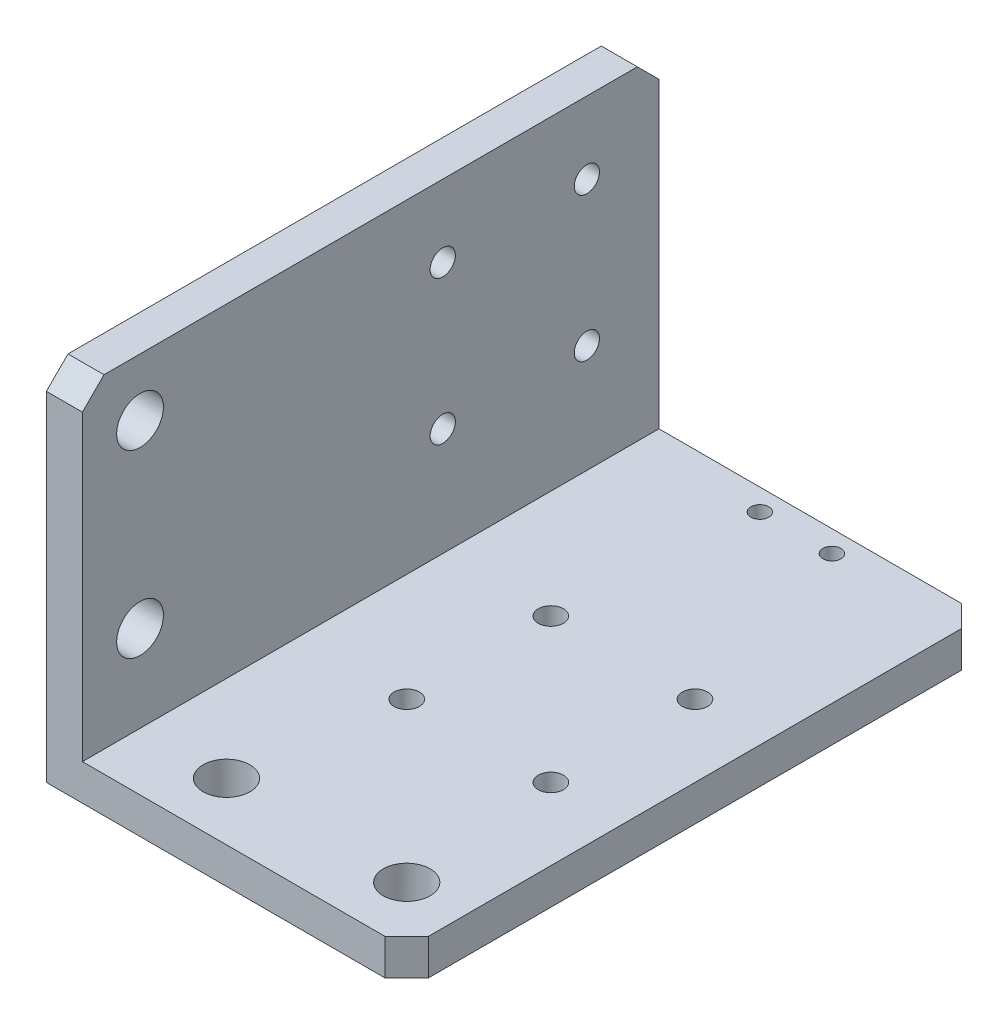
SolidWorks part; units mm, degrees
material "Lega 1060"
ref_plane "Piano frontale" through (0, 0, 0) normal (0, 0, 1) x (1, 0, 0)
ref_plane "Piano superiore" through (0, 0, 0) normal (0, 1, 0) x (1, 0, 0)
ref_plane "Piano destro" through (0, 0, 0) normal (1, 0, 0) x (0, 0, -1)
sketch "Schizzo1" plane through (0, 0, 0) normal (0, 0, 1) x (1, 0, 0)
  line L0 (0, 0) -> (0, 50)
  line L1 (0, 50) -> (5, 50)
  line L2 (5, 50) -> (5, 5)
  line L3 (5, 5) -> (50, 5)
  line L4 (50, 5) -> (50, 0)
  line L5 (50, 0) -> (0, 0)
  dimension "D1" = 5
  dimension "D2" = 5
  dimension "D3" = 50
  dimension "D4" = 50
extrude "Estrusione-Estrusione1" add sketch "Schizzo1" along normal blind 80
sketch "Schizzo2" plane through (0, 0, 0) normal (0, -1, 0) x (1, 0, 0)
  line L0 (5.4524, 72) -> (42.7933, 72) construction
  line L1 (0, 80) -> (50, 80) construction
  line L5 (50, 80) -> (50, 0) construction
  point P4 (17, 72)
  point P5 (42, 72)
  dimension "D1" = 8
  dimension "D2" = 25
  dimension "D3" = 8
sketch "Schizzo3" plane through (0, 0, 0) normal (-1, 0, 0) x (0, 0, 1)
  line L0 (72, 44.621) -> (72, 5.772) construction
  line L1 (80, 50) -> (80, 0) construction
  line L2 (80, 50) -> (0, 50) construction
  point P4 (72, 42)
  point P5 (72, 17)
  dimension "D1" = 8
  dimension "D2" = 8
  dimension "D3" = 25
hole_wizard "Foro Ø6.5 (6.5)-1" positions "Schizzo5" profile "Schizzo4" hole size "Ø6.5" standard "ISO" end condition through all
sketch "Schizzo5" plane through (0, 0, 0) normal (0, -1, 0) x (-1, 0, 0)
  point P0 (-17, -72)
  point P3 (-42, -72)
sketch "Schizzo4" plane through (17, 0, 72) normal (1, 0, 0) x (0, 0, -1)
  line L0 (0, 0) -> (0, 50)
  line L1 (0, 50) -> (3.25, 50)
  line L2 (3.25, 50) -> (3.25, 0)
  line L5 (3.25, 0) -> (0, 0)
  line L11 (0, -6.35) -> (0, 107.95) construction
  dimension "Thru Hole Dia." = 6.5
  dimension "Thru Hole Depth" = 50
hole_wizard "Foro Ø6.5 (6.5)-2" positions "Schizzo7" profile "Schizzo6" hole size "Ø6.5" standard "ISO"
sketch "Schizzo7" plane through (0, 0, 0) normal (-1, 0, 0) x (0, 0, 1)
  point P1 (72, 42)
  point P4 (72, 17)
sketch "Schizzo6" plane through (0, 42, 72) normal (0, 1, 0) x (0, 0, 1)
  line L0 (0, 0) -> (0, 6.9528)
  line L1 (0, 6.9528) -> (3.25, 5)
  line L2 (3.25, 5) -> (3.25, 0)
  line L5 (3.25, 0) -> (0, 0)
  line L10 (0, 6.9528) -> (-3.25, 5) construction
  line L11 (0, -6.35) -> (0, 107.95) construction
  dimension "Hole Dia." = 6.5
  dimension "Hole Depth" = 5
  dimension "Drill Angle" = 118
ref_plane "Piano1" through (0, 0, 40) normal (0, 0, 1) x (1, 0, 0)
sketch "Schizzo8" plane through (0, 0, 0) normal (-1, 0, 0) x (0, 0, 1)
  line L2 (80, 50) -> (80, 0) construction
  line L3 (80, 50) -> (0, 50) construction
  circle A0 centre (20, 30) radius 7
  dimension "D3" = 14
  dimension "D1" = 60
  dimension "D2" = 20
sketch "Schizzo9" plane through (0, 0, 0) normal (0, -1, 0) x (1, 0, 0)
  line L0 (50, 80) -> (50, 0) construction
  line L1 (0, 80) -> (50, 80) construction
  circle A0 centre (30, 40) radius 7
  dimension "D1" = 14
  dimension "D2" = 20
  dimension "D3" = 40
sketch "Schizzo10" plane through (0, 0, 0) normal (-1, 0, 0) x (0, 0, 1)
  line L1 (20, 42.2663) -> (20, 14.8621) construction
  line L2 (19.1906, 30.8094) -> (20, 30) construction
  circle A0 centre (10, 40) radius 1.75
  circle A1 centre (30, 40) radius 1.75
  circle A3 centre (30, 20) radius 1.75
  circle A4 centre (10, 20) radius 1.75
  circle A5 centre (20, 30) radius 7 construction
  point P20 (20, 30)
  dimension "D1" = 3.5
  dimension "D2" = 20
  dimension "D3" = 45
  dimension "D4" = 4
extrude "Taglio-Estrusione3" cut sketch "Schizzo10" against normal up to next
sketch "Schizzo11" plane through (0, 0, 0) normal (0, -1, 0) x (1, 0, 0)
  line L0 (30, 40) -> (14.4837, 40) construction
  line L1 (30, 40) -> (34.5929, 44.5929) construction
  circle A0 centre (20, 30) radius 1.75
  circle A3 centre (20, 50) radius 1.75
  circle A4 centre (40, 50) radius 1.75
  circle A5 centre (40, 30) radius 1.75
  circle A6 centre (30, 40) radius 7 construction
  point P2 (30, 40)
  point P17 (30, 40)
  dimension "D2" = 3.5
  dimension "D1" = 20
  dimension "D3" = 45
  dimension "D4" = 4
extrude "Taglio-Estrusione4" cut sketch "Schizzo11" against normal up to next
chamfer "Smusso1" distance 3 angle 45 4 edges at (2.5, 50, 0) (50, 2.5, 0) (2.5, 50, 80) (50, 2.5, 80)
sketch "Schizzo12" plane through (0, 5, 0) normal (0, 1, 0) x (1, 0, 0)
  line L0 (50, -77) -> (50, -3) construction
  line L1 (47, 0) -> (5, 0) construction
  circle A0 centre (32, -3) radius 1.25
  circle A1 centre (22, -3) radius 1.25
  dimension "D1" = 2.5
  dimension "D3" = 18
  dimension "D4" = 3
  dimension "D2" = 10
extrude "Taglio-Estrusione5" cut sketch "Schizzo12" against normal up to next
